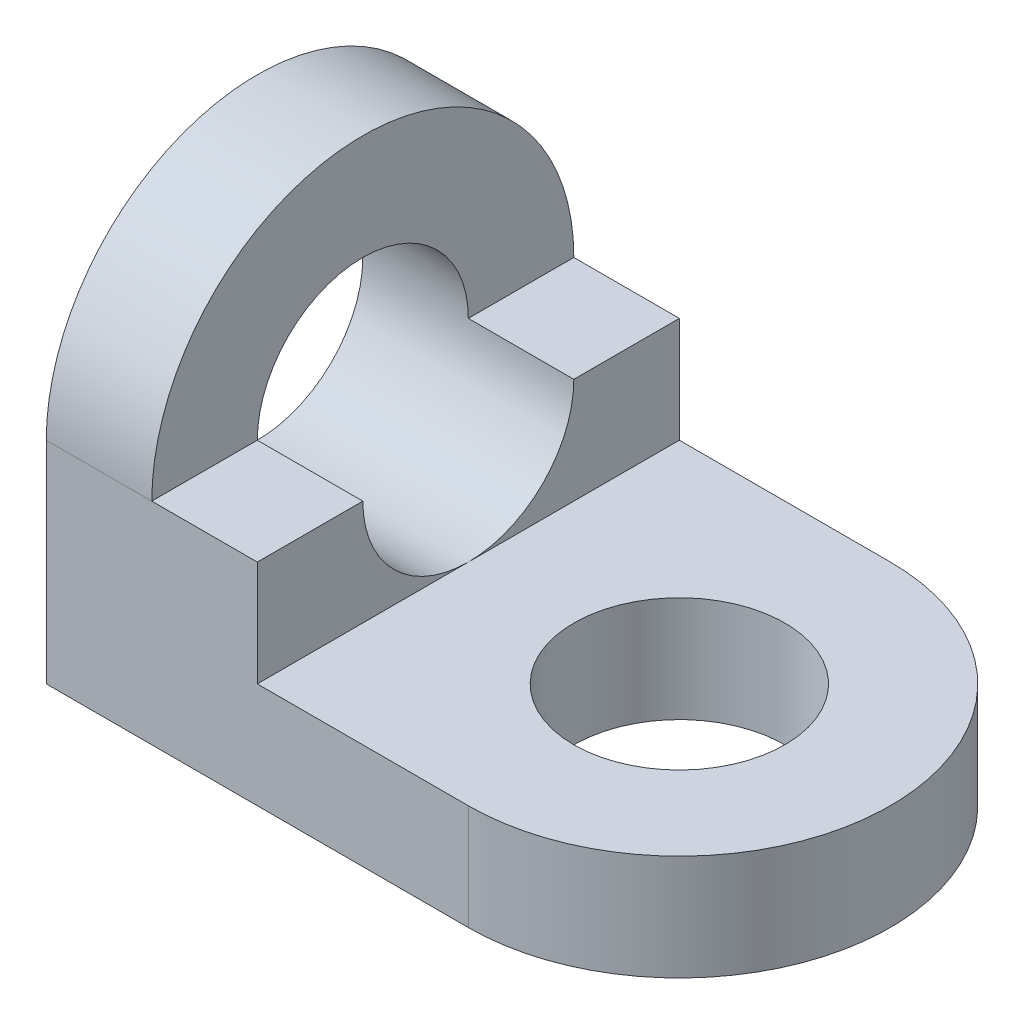
SolidWorks part; units mm, degrees
ref_plane "前基準面" through (0, 0, 0) normal (0, 0, 1) x (1, 0, 0)
ref_plane "上基準面" through (0, 0, 0) normal (0, 1, 0) x (1, 0, 0)
ref_plane "右基準面" through (0, 0, 0) normal (1, 0, 0) x (0, 0, -1)
sketch "草圖1" plane through (0, 0, 0) normal (0, 1, 0) x (1, 0, 0)
  line L0 (0, 0) -> (4, 0) construction
  line L1 (4, 2) -> (0, 2)
  line L2 (0, 2) -> (0, -2)
  line L3 (0, -2) -> (4, -2)
  circle A0 centre (4, 0) radius 1
  arc A1 (4, -2) -> (4, 2) centre (4, 0) ccw
  dimension "D1" = 2
  dimension "D2" = 4
  dimension "D3" = 4
extrude "填料-伸長1" add sketch "草圖1" along normal blind 1
sketch "草圖2" plane through (0, 0, 0) normal (1, 0, 0) x (0, 0, -1)
  line L0 (0, 0) -> (0, 13.6598) construction
  line L1 (-2, 2) -> (4.4405, 2) construction
  line L2 (-2, 2) -> (-2, 0)
  line L3 (-10, 1) -> (2, 1)
  line L4 (2, 1) -> (2, 2)
  line L5 (-2, 0) -> (2, 0)
  line L6 (2, 0) -> (2, 2)
  line L7 (-1, 2) -> (-2, 2)
  line L8 (1, 2) -> (2, 2)
  circle A0 centre (0, 2) radius 1
  arc A1 (2, 2) -> (-2, 2) centre (0, 2) ccw
  dimension "D2" = 2
  dimension "D3" = 4
  dimension "D1" = 2
extrude "填料-伸長3" add sketch "草圖2" along normal blind 1 contours L5 L6 L3 L2 | A1 L2 L5 L6 | A0 region at (0, 0.5, 0)
extrude "填料-伸長4" add sketch "草圖2<4>" along normal blind 2 contours L5 L6 L3 L2 | A0 L7 L2 L3 | A0 L3 L4 L8 region at (0, 1.4511, 1.3722) region at (0, 0.5, 0) region at (0, 1.4511, -1.3722)
sketch "草圖2<4>" plane through (0, 0, 0) normal (1, 0, 0) x (0, 0, -1) same geometry as "草圖2"
